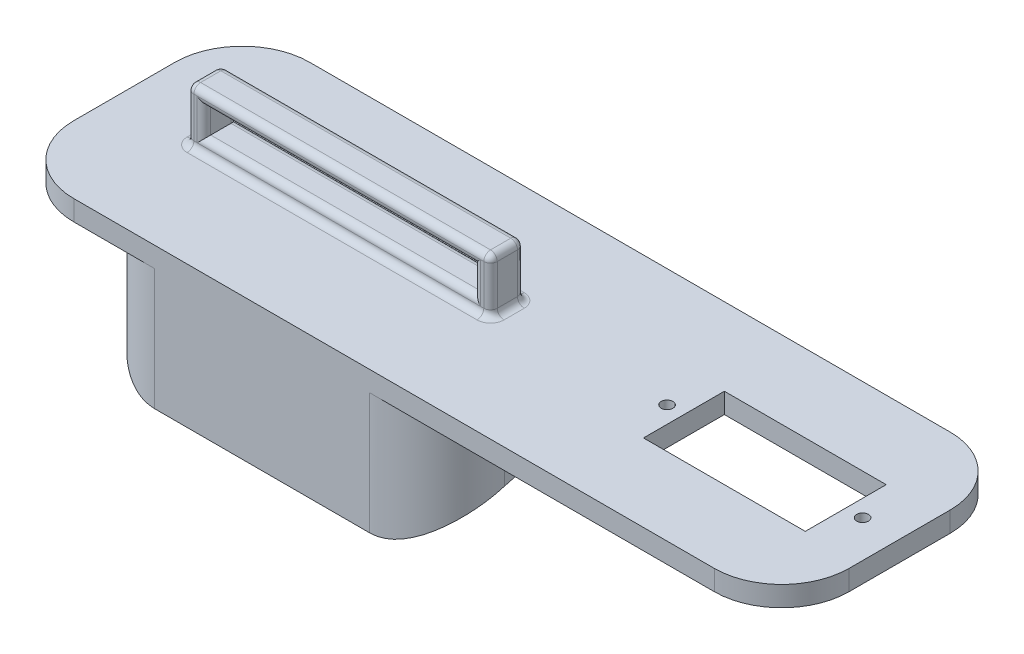
SolidWorks part; units mm, degrees
ref_plane "Front Plane" through (0, 0, 0) normal (0, 0, 1) x (1, 0, 0)
ref_plane "Top Plane" through (0, 0, 0) normal (0, 1, 0) x (1, 0, 0)
ref_plane "Right Plane" through (0, 0, 0) normal (1, 0, 0) x (0, 0, -1)
sketch "Sketch1" plane through (0, 0, 0) normal (0, 1, 0) x (1, 0, 0)
  line L1 (57.5, -17.5) -> (-57.5, -17.5)
  line L2 (57.5, -17.5) -> (57.5, 17.5)
  line L3 (57.5, 17.5) -> (-57.5, 17.5)
  line L4 (-57.5, -17.5) -> (-57.5, 17.5)
  line L5 (57.5, -17.5) -> (-57.5, 17.5) construction
  line L6 (57.5, 17.5) -> (-57.5, -17.5) construction
  point P0 (0, 0)
  dimension "D1" = 115
  dimension "D2" = 35
extrude "Boss-Extrude1" add sketch "Sketch1" along normal blind 3
fillet "Fillet1" radius 10 4 edges at (57.5, 1.5, -17.5) (57.5, 1.5, 17.5) (-57.5, 1.5, 17.5) (-57.5, 1.5, -17.5)
sketch "Sketch2" plane through (0, 3, 0) normal (0, 1, 0) x (1, 0, 0)
  line L1 (-46, -2.1845) -> (-1, -2.1845)
  line L2 (-46, -2.1845) -> (-46, 2.8155)
  line L3 (-46, 2.8155) -> (-1, 2.8155)
  line L4 (-1, -2.1845) -> (-1, 2.8155)
  line L5 (-46, -2.1845) -> (-1, 2.8155) construction
  line L6 (-46, 2.8155) -> (-1, -2.1845) construction
  point P0 (-23.5, 0.3155)
  dimension "D1" = 45
  dimension "D2" = 5
  dimension "D3" = 1
extrude "Boss-Extrude2" add sketch "Sketch2" along normal blind 8
sketch "Sketch3" plane through (0, 0, 2.1845) normal (0, 0, 1) x (1, 0, 0)
  line L0 (-1, 11) -> (-1, 3) construction
  line L1 (-3.5, 5) -> (-43.5, 5)
  line L2 (-3.5, 5) -> (-3.5, 9)
  line L3 (-3.5, 9) -> (-43.5, 9)
  line L4 (-43.5, 5) -> (-43.5, 9)
  line L5 (-3.5, 5) -> (-43.5, 9) construction
  line L6 (-3.5, 9) -> (-43.5, 5) construction
  line L7 (-46, 11) -> (-1, 11) construction
  point P0 (-23.5, 7)
  dimension "D1" = 40
  dimension "D2" = 2.5
  dimension "D3" = 2
  dimension "D4" = 4
extrude "Cut-Extrude1" cut sketch "Sketch3" against normal through all
fillet "Fillet2" radius 1 19 edges at (-23.5, 3, -2.8155) (-46, 3, -0.3155) (-1, 3, -0.3155) (-46, 7, 2.1845) (-23.5, 11, 2.1845) (-1, 7, 2.1845) (-23.5, 3, 2.1845) (-3.5, 7, 2.1845) (-23.5, 9, 2.1845) (-43.5, 7, 2.1845) (-23.5, 5, 2.1845) (-43.5, 7, -2.8155) (-23.5, 5, -2.8155) (-46, 11, -0.3155) (-1, 11, -0.3155) (-1, 7, -2.8155) (-23.5, 11, -2.8155) (-46, 7, -2.8155) (-23.5, 9, -2.8155)
sketch "Sketch4" plane through (0, 3, 0) normal (0, 1, 0) x (1, 0, 0)
  line L0 (57.5, -7.5) -> (57.5, 7.5) construction
  line L1 (49.5, -6) -> (25.5, -6)
  line L2 (49.5, -6) -> (49.5, 6)
  line L3 (49.5, 6) -> (25.5, 6)
  line L4 (25.5, -6) -> (25.5, 6)
  line L5 (49.5, -6) -> (25.5, 6) construction
  line L6 (49.5, 6) -> (25.5, -6) construction
  point P0 (37.5, 0)
  dimension "D1" = 24
  dimension "D2" = 8
  dimension "D3" = 12
extrude "Cut-Extrude2" cut sketch "Sketch4" against normal through all contours L3 L4 L1 L2
sketch "Sketch11" plane through (0, 0, 0) normal (0, -1, 0) x (-1, 0, 0)
  line L0 (-6.3696, 0) -> (-6.3696, -17.5)
  line L1 (47.5, -17.5) -> (-47.5, -17.5) construction
  line L2 (-6.3696, -17.5) -> (45.4998, -17.5)
  line L3 (45.4998, -17.5) -> (45.4998, 17.5362)
  line L4 (45.4998, 17.5362) -> (-6.3696, 17.5)
  line L5 (-47.5, 17.5) -> (47.5, 17.5) construction
  line L6 (-6.3696, 17.5) -> (-6.3696, 0)
extrude "Boss-Extrude3" add sketch "Sketch11" along normal blind 18
fillet "Fillet3" radius 10 2 edges at (-45.4998, -9, -17.5362) (-45.4998, -9, 17.5)
fillet "Fillet4" radius 10 2 edges at (6.3696, -9, -17.5) (6.3696, -9, 17.5)
sketch "Sketch12" plane through (0, 3, 0) normal (0, 1, 0) x (1, 0, 0)
  line L0 (25.5, -6) -> (25.5, 6) construction
  line L1 (37.5, 6) -> (37.5, -24.1211) construction
  line L2 (49.5, 6) -> (25.5, 6) construction
  circle A0 centre (23, 0) radius 0.875
  circle A1 centre (52, 0) radius 0.875
  dimension "D1" = 2.5
  dimension "D2" = 1.75
extrude "Cut-Extrude3" cut sketch "Sketch12" against normal through all
sketch "Sketch13" plane through (-45.4998, 0, 0) normal (-1, 0, 0) x (0, 0, 1)
  line L0 (-17.5292, -18) -> (17.5, -18)
  arc A0 (-17.5292, -18) -> (17.5, -18) centre (-0.0146, -35.9657) cw
  point P3 (-17.5292, -18)
extrude "Cut-Extrude4" cut sketch "Sketch13" against normal blind 58
